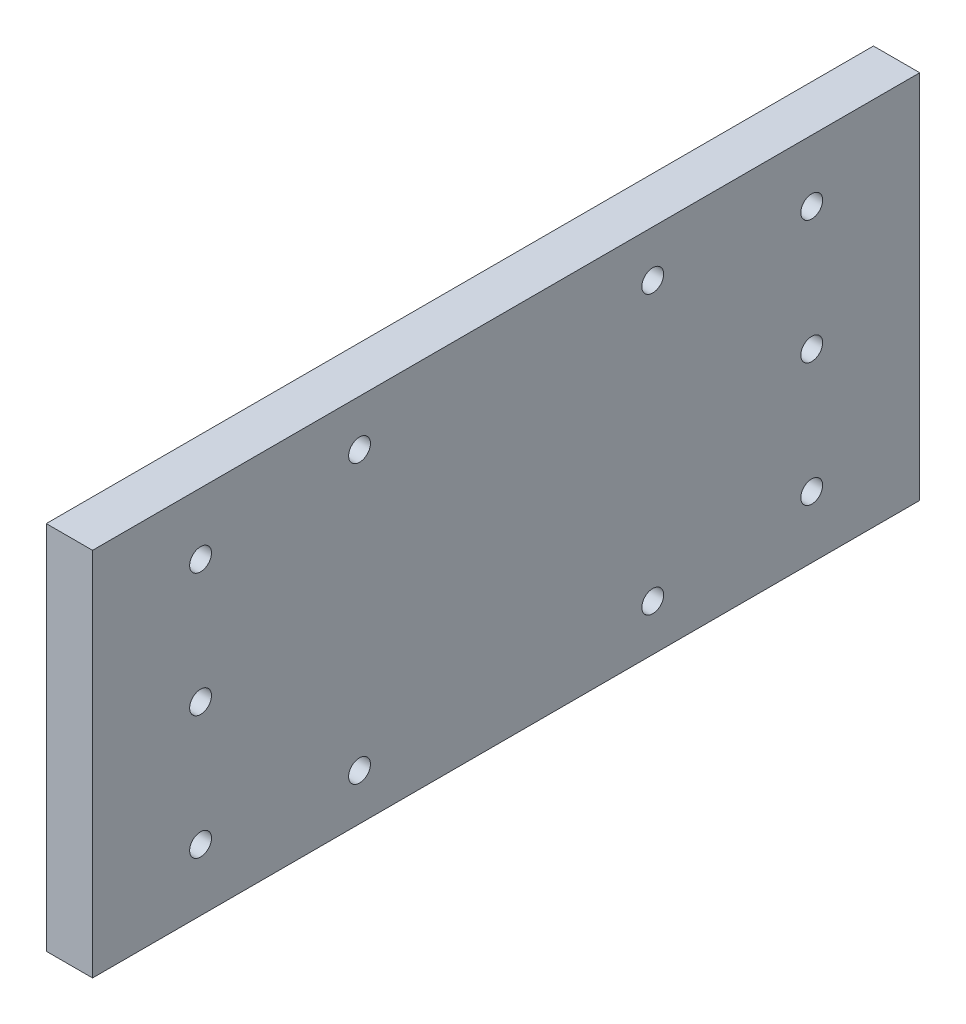
SolidWorks part; units mm, degrees
material "AISI 1015 Steel, Cold Drawn (SS)"
ref_plane "Front Plane" through (0, 0, 0) normal (0, 0, 1) x (1, 0, 0)
ref_plane "Top Plane" through (0, 0, 0) normal (0, 1, 0) x (1, 0, 0)
ref_plane "Right Plane" through (0, 0, 0) normal (1, 0, 0) x (0, 0, -1)
sketch "Sketch1" plane through (0, 0, 0) normal (0, 0, 1) x (1, 0, 0)
  line L1 (-4.7625, 38.1) -> (4.7625, 38.1)
  line L2 (-4.7625, 38.1) -> (-4.7625, -38.1)
  line L3 (-4.7625, -38.1) -> (4.7625, -38.1)
  line L4 (4.7625, 38.1) -> (4.7625, -38.1)
  line L5 (-4.7625, 38.1) -> (4.7625, -38.1) construction
  line L6 (-4.7625, -38.1) -> (4.7625, 38.1) construction
  point P0 (0, 0)
  dimension "D1" = 9.525
  dimension "D2" = 76.2
extrude "Boss-Extrude1" add sketch "Sketch1" along normal blind 170.18
hole_wizard "#8 Clearance Hole1" positions "Sketch3" profile "Sketch2" hole size "#8" standard "ANSI Inch" end condition through all
sketch "Sketch3" plane through (4.7625, 0, 0) normal (1, 0, 0) x (0, 0, -1)
  line L0 (-170.18, -38.1) -> (0, -38.1) construction
  line L1 (-170.18, -38.1) -> (-170.18, 38.1) construction
  line L2 (0, -38.1) -> (0, 38.1) construction
  point P0 (-147.955, 25.4)
  point P2 (-147.955, 0)
  point P4 (-147.955, -25.4)
  point P6 (-22.225, 25.4)
  point P8 (-22.225, 0)
  point P10 (-22.225, -25.4)
  point P17 (-170.18, 0)
  dimension "D1" = 25.4
  dimension "D2" = 25.4
  dimension "D3" = 12.7
  dimension "D4" = 22.225
  dimension "D5" = 22.225
sketch "Sketch2" plane through (4.7625, 25.4, 147.955) normal (0, 1, 0) x (0, 0, -1)
  line L0 (0, 0) -> (0, 9.525)
  line L1 (0, 9.525) -> (2.2479, 9.525)
  line L2 (2.2479, 9.525) -> (2.2479, 0)
  line L5 (2.2479, 0) -> (0, 0)
  line L11 (0, -6.35) -> (0, 107.95) construction
  dimension "Thru Hole Dia." = 4.4958
  dimension "Thru Hole Depth" = 9.525
hole_wizard "#8 Clearance Hole2" positions "Sketch4" profile "Sketch5" hole size "#8" standard "ANSI Inch" end condition through all
sketch "Sketch4" plane through (4.7625, 0, 0) normal (1, 0, 0) x (0, 0, -1)
  line L0 (-170.18, 38.1) -> (-115.2525, 28.575) construction
  line L2 (-115.2525, -28.575) -> (-170.18, -38.1) construction
  line L5 (-54.9275, -28.575) -> (0, -38.1) construction
  line L8 (-54.9275, 28.575) -> (0, 38.1) construction
  point P0 (-115.2525, 28.575)
  point P2 (-54.9275, 28.575)
  point P4 (-54.9275, -28.575)
  point P6 (-115.2525, -28.575)
  dimension "D1" = 60.325
  dimension "D2" = 57.15
sketch "Sketch5" plane through (4.7625, 28.575, 115.2525) normal (0, 1, 0) x (0, 0, -1)
  line L0 (0, 0) -> (0, 9.525)
  line L1 (0, 9.525) -> (2.2479, 9.525)
  line L2 (2.2479, 9.525) -> (2.2479, 0)
  line L5 (2.2479, 0) -> (0, 0)
  line L11 (0, -6.35) -> (0, 107.95) construction
  dimension "Thru Hole Dia." = 4.4958
  dimension "Thru Hole Depth" = 9.525
